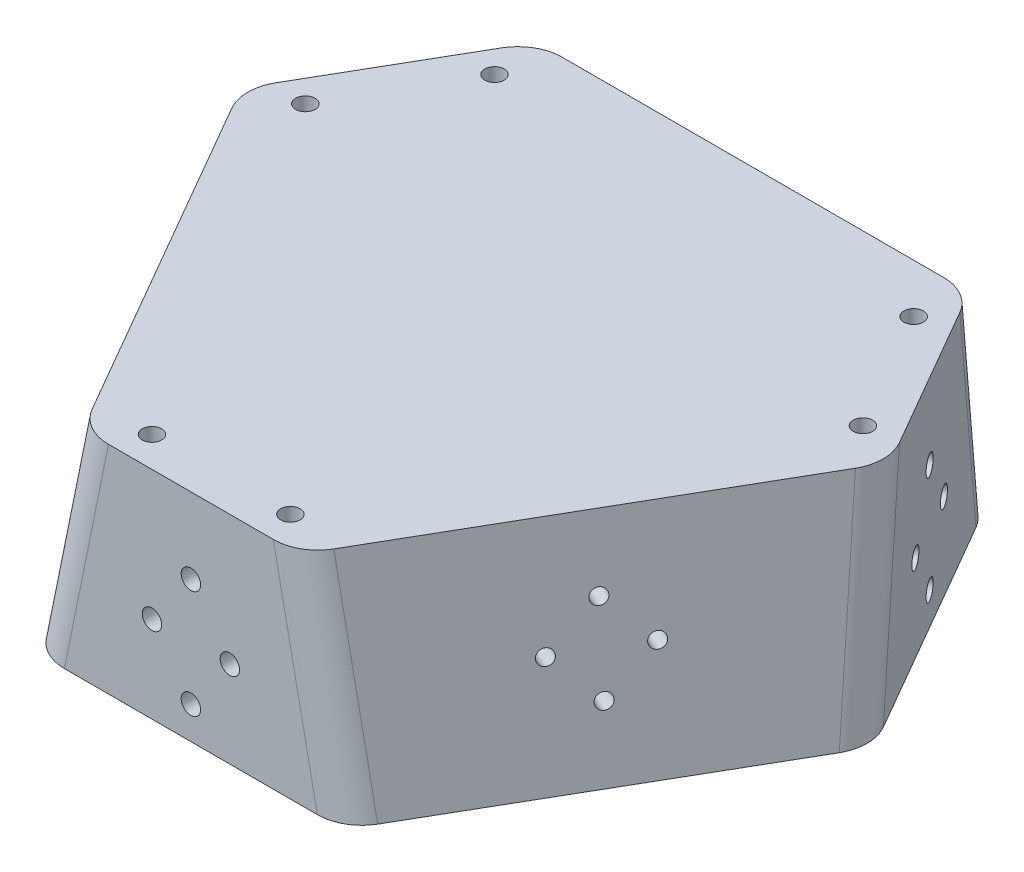
SolidWorks part; units mm, degrees
note: '?' marks a value the reader was unsure of.
ref_plane "Front Plane" through (0, 0, 0) normal (0, 0, 1) x (1, 0, 0)
ref_plane "Top Plane" through (0, 0, 0) normal (0, 1, 0) x (1, 0, 0)
ref_plane "Right Plane" through (0, 0, 0) normal (1, 0, 0) x (0, 0, -1)
sketch "Sketch1" plane through (0, 0, 0) normal (0, 1, 0) x (1, 0, 0)
  line L0 (-50, 57.735) -> (50, 57.735)
  line L1 (75, 14.4338) -> (25, -72.1688)
  line L2 (-25, -72.1688) -> (-75, 14.4338)
  line L3 (0, 0) -> (-50, -28.8675) construction
  line L4 (0, 0) -> (0, 57.735) construction
  line L5 (0, 0) -> (50, -28.8675) construction
  line L6 (-50, 57.735) -> (-75, 14.4338)
  line L7 (-25, -72.1688) -> (25, -72.1688)
  line L8 (50, 57.735) -> (75, 14.4338)
  line L9 (-100, 57.735) -> (-50, 57.735) construction
  line L10 (-75, 14.4338) -> (-100, 57.735) construction
  line L11 (50, 57.735) -> (100, 57.735) construction
  line L12 (100, 57.735) -> (75, 14.4338) construction
  line L13 (25, -72.1688) -> (0, -115.4701) construction
  line L14 (0, -115.4701) -> (-25, -72.1688) construction
  dimension "D1" = 50
  dimension "D2" = 100
extrude "Boss-Extrude1" add sketch "Sketch1" along normal blind 50
ref_plane "Plane2" through (0, 0, 0) normal (0.5, 0, -0.866) x (-0.866, 0, -0.5)
ref_plane "Plane3" through (0, 0, 0) normal (-0.5, 0, -0.866) x (-0.866, 0, 0.5)
sketch "Sketch2" plane through (0, 0, 0) normal (1, 0, 0) x (0, 0, -1)
  line L0 (57.735, 50) -> (66.5514, 0)
  line L1 (66.5514, 0) -> (57.735, 0)
  line L4 (14.4338, 0) -> (57.735, 0)
  line L5 (57.735, 0) -> (57.735, 50)
  line L6 (57.735, 50) -> (14.4338, 50)
  line L7 (14.4338, 50) -> (14.4338, 0)
  line L8 (14.4338, 0) -> (57.735, 0) construction
  line L9 (57.735, 0) -> (57.735, 50)
  line L10 (57.735, 50) -> (14.4338, 50) construction
  line L11 (14.4338, 50) -> (14.4338, 0) construction
  dimension "ThrusterAngle" = 10
extrude "Boss-Extrude2" add sketch "Sketch2" along normal up to surface and the other way up to surface up to face at (62.5, 25, -36.0844) other way up to face at (-62.5, 25, -36.0844)
sketch "Sketch7" plane through (0, 0, 0) normal (-0.5, 0, -0.866) x (-0.866, 0, 0.5)
  line L0 (57.735, 50) -> (57.735, 0) construction
  line L1 (57.735, 50) -> (57.735, 0)
  line L2 (57.735, 50) -> (66.5514, 0)
  line L3 (66.5514, 0) -> (57.735, 0)
  dimension "D1" = 10
extrude "Boss-Extrude3" add sketch "Sketch7" along normal up to surface and the other way up to surface up to face at (-61.2275, 25, -38.2885) other way up to face at (0, 25, 72.1688)
sketch "Sketch8" plane through (0, 0, 0) normal (0.5, 0, -0.866) x (-0.866, 0, -0.5)
  line L0 (-57.735, 50) -> (-57.735, 0) construction
  line L1 (-57.735, 50) -> (-57.735, 0)
  line L2 (-57.735, 50) -> (-66.5514, 0)
  line L3 (-66.5514, 0) -> (-57.735, 0)
  dimension "D1" = 10
extrude "Boss-Extrude4" add sketch "Sketch8" along normal up to surface and the other way up to surface up to face at (61.2275, 25, -38.2885) other way up to face at (-2.5451, 25, 72.1688)
sketch "Sketch9" plane through (0, 0, 0) normal (0, -1, 0) x (1, 0, 0)
  line L0 (-57.6795, -14.4338) -> (-41.3397, -42.735)
  line L1 (-41.3397, -42.735) -> (41.3397, -42.735)
  line L2 (41.3397, -42.735) -> (57.6795, -14.4338)
  line L3 (57.6795, -14.4338) -> (16.3397, 57.1688)
  line L4 (16.3397, 57.1688) -> (-16.3397, 57.1688)
  line L5 (-16.3397, 57.1688) -> (-57.6795, -14.4338)
  line L6 (-75, -14.4338) -> (-50, -57.735)
  line L7 (-25, 72.1688) -> (-75, -14.4338)
  line L8 (25, 72.1688) -> (-25, 72.1688)
  line L9 (75, -14.4338) -> (25, 72.1688)
  line L10 (50, -57.735) -> (75, -14.4338)
  line L11 (-50, -57.735) -> (50, -57.735)
  line L12 (-75, -14.4338) -> (-50, -57.735) construction
  line L13 (-25, 72.1688) -> (-75, -14.4338) construction
  line L14 (25, 72.1688) -> (-25, 72.1688) construction
  line L15 (75, -14.4338) -> (25, 72.1688) construction
  line L16 (50, -57.735) -> (75, -14.4338) construction
  line L17 (-50, -57.735) -> (50, -57.735) construction
  dimension "D1" = 0
  dimension "D2" = 15
extrude "Cut-Extrude1" cut sketch "Sketch9" against normal offset from surface (40 mm away) 10 up to face at (0, 50, 0)
ref_axis "Axis1" through (0, -2.5, 0) along (0, 1, 0)?
sketch "Sketch3" plane through (0, 11.381, -64.5446) normal (0, 0.1736, -0.9848) x (-1, 0, 0)
  line L0 (0, 39.2148) -> (0, 13.8291) construction
  line L1 (-50, 39.2148) -> (50, 39.2148) construction
  line L2 (0, 13.8291) -> (0, -11.5565) construction
  line L3 (-44.9099, -11.5565) -> (44.9099, -11.5565) construction
  line L4 (0, 23.3291) -> (9.5, 13.8291) construction
  line L5 (0, 23.3291) -> (-9.5, 13.8291) construction
  line L6 (9.5, 13.8291) -> (0, 4.3291) construction
  line L7 (-9.5, 13.8291) -> (0, 4.3291) construction
  line L8 (0, 23.3291) -> (0, 4.3291) construction
  line L9 (9.5, 13.8291) -> (-9.5, 13.8291) construction
  dimension "D1" = 19
  dimension "D2" = 19
hole_wizard "M3 Clearance Hole1" positions "3DSketch1" profile "Sketch10" hole size "M3" standard "ANSI Metric"
sketch3d "3DSketch1"
  point P0 (0, 34.3557, -60.4935)
  point P3 (9.5, 25, -62.1432)
  point P6 (0, 15.6443, -63.7929)
  point P9 (-9.5, 25, -62.1432)
sketch "Sketch10" plane through (0, 34.3557, -60.4935) normal (1, 0, 0) x (0, 0.9848, 0.1736)
  line L0 (0, 0) -> (0, 50)
  line L1 (0, 50) -> (1.7, 48.9785)
  line L2 (1.7, 48.9785) -> (1.7, 0)
  line L5 (1.7, 0) -> (0, 0)
  line L10 (0, 50) -> (-1.7, 48.9785) construction
  line L11 (0, -6.35) -> (0, 107.95) construction
  dimension "Hole Dia." = 3.4
  dimension "Hole Depth" = 50
  dimension "Drill Angle" = 118
pattern_circular "CirPattern6" count 3 every 120 about axis through (0, -2.5, 0) along (0, 1, 0) of "M3 Clearance Hole1"
sketch "Sketch12" plane through (-49.5096, 0, -28.5844) normal (0.866, 0, 0.5) x (0.5, 0, -0.866)
  line L0 (-16.3397, 20) -> (16.3397, 20) construction
  line L1 (-16.3397, 40) -> (-16.3397, 0) construction
  line L2 (16.3397, 40) -> (16.3397, 0) construction
  line L3 (0, 40) -> (0, 0) construction
  line L4 (16.3397, 40) -> (-16.3397, 40) construction
  line L5 (-16.3397, 0) -> (16.3397, 0) construction
  line L6 (-9, 20) -> (0, 32.5) construction
  line L7 (-4.525, 17.4164) -> (-4.525, 22.5836)
  line L8 (-4.525, 22.5836) -> (-9, 25.1673)
  line L9 (-9, 25.1673) -> (-13.475, 22.5836)
  line L10 (-13.475, 22.5836) -> (-13.475, 17.4164)
  line L11 (-13.475, 17.4164) -> (-9, 14.8327)
  line L12 (-9, 14.8327) -> (-4.525, 17.4164)
  line L13 (9, 14.8327) -> (13.475, 17.4164)
  line L14 (13.475, 17.4164) -> (13.475, 22.5836)
  line L15 (13.475, 22.5836) -> (9, 25.1673)
  line L16 (9, 25.1673) -> (4.525, 22.5836)
  line L17 (4.525, 22.5836) -> (4.525, 17.4164)
  line L18 (4.525, 17.4164) -> (9, 14.8327)
  line L19 (4.475, 4.9164) -> (4.475, 10.0836)
  line L20 (4.475, 10.0836) -> (0, 12.6673)
  line L21 (0, 12.6673) -> (-4.475, 10.0836)
  line L22 (-4.475, 10.0836) -> (-4.475, 4.9164)
  line L23 (-4.475, 4.9164) -> (0, 2.3327)
  line L24 (0, 2.3327) -> (4.475, 4.9164)
  line L25 (4.475, 29.9164) -> (4.475, 35.0836)
  line L26 (4.475, 35.0836) -> (0, 37.6673)
  line L27 (0, 37.6673) -> (-4.475, 35.0836)
  line L28 (-4.475, 35.0836) -> (-4.475, 29.9164)
  line L29 (-4.475, 29.9164) -> (0, 27.3327)
  line L30 (0, 27.3327) -> (4.475, 29.9164)
  line L31 (0, 32.5) -> (9, 20) construction
  line L32 (9, 20) -> (0, 7.5) construction
  line L33 (0, 7.5) -> (-9, 20) construction
  circle A0 centre (-9, 20) radius 4.475 construction
  circle A1 centre (9, 20) radius 4.475 construction
  circle A2 centre (0, 7.5) radius 4.475 construction
  circle A3 centre (0, 32.5) radius 4.475 construction
  point P48 (0, 32.5)
  point P51 (-9, 20)
  point P54 (9, 20)
  point P57 (0, 7.5)
  dimension "D1" = 8.95
  dimension "D2" = 25
  dimension "D3" = 18
extrude "Cut-Extrude2" cut sketch "Sketch12" against normal blind 3.5
sketch "Sketch13" plane through (-52.5407, 0, -30.3344) normal (0.866, 0, 0.5) x (0.5, 0, -0.866)
  point P0 (-9, 20)
  point P1 (9, 20)
  point P2 (0, 7.5)
  point P3 (0, 32.5)
hole_wizard "#8 Clearance Hole1" positions "Sketch13" profile "Sketch14" hole size "#8" standard "ANSI Inch"
sketch "Sketch14" plane through (-57.0407, 20, -22.5402) normal (0, 1, 0) x (0.5, 0, -0.866)
  line L0 (0, 0) -> (0, 50)
  line L1 (0, 50) -> (2.2479, 48.6493)
  line L2 (2.2479, 48.6493) -> (2.2479, 0)
  line L5 (2.2479, 0) -> (0, 0)
  line L10 (0, 50) -> (-2.2479, 48.6493) construction
  line L11 (0, -6.35) -> (0, 107.95) construction
  dimension "Hole Dia." = 4.4958
  dimension "Hole Depth" = 50
  dimension "Drill Angle" = 118
sketch "Sketch15" plane through (0, 50, 0) normal (0, 1, 0) x (1, 0, 0)
  line L0 (-64.4378, 18.728) -> (-48.4378, 46.4408) construction
  line L1 (-50, 57.735) -> (-75, 14.4338) construction
  line L2 (-64.4378, 18.728) -> (-75, 14.4338) construction
  line L3 (-48.4378, 46.4408) -> (-50, 57.735) construction
  point P9 (-64.4378, 18.728)
  point P10 (-48.4378, 46.4408)
  dimension "D1" = 7
  dimension "D2" = 32
sketch "Sketch18" plane through (0, 0, 0) normal (0, -1, 0) x (1, 0, 0)
  point P0 (-64.4378, -18.728)
  point P1 (-48.4378, -46.4408)
hole_wizard "CBORE for #8 Socket Head Cap Screw1" positions "Sketch18" profile "Sketch19" counterbore size "#8" standard "ANSI Inch"
sketch "Sketch19" plane through (-64.4378, 0, -18.728) normal (1, 0, 0) x (0, 0, -1)
  line L0 (0, 0) -> (0, 60)
  line L1 (0, 60) -> (2.2479, 58.6493)
  line L2 (2.2479, 58.6493) -> (2.2479, 12.7)
  line L3 (2.2479, 12.7) -> (3.9687, 12.7)
  line L4 (3.9687, 12.7) -> (3.9688, 0)
  line L5 (3.9688, 0) -> (0, 0)
  line L10 (0, 60) -> (-2.2479, 58.6493) construction
  line L11 (0, -6.35) -> (0, 107.95) construction
  dimension "Hole Dia." = 4.4958
  dimension "Hole Depth" = 60
  dimension "C'Bore Dia." = 7.9375
  dimension "C'Bore Depth" = 12.7
  dimension "Drill Angle" = 118
pattern_circular "CirPattern7" count 3 every 120 about axis through (0, 0, 0) along (0, 1, 0) of "#8 Clearance Hole1", "Cut-Extrude2", "CBORE for #8 Socket Head Cap Screw1"
sketch "Be Happy" plane through (0, 50, 0) normal (0, 1, 0) x (1, 0, 0)
  line L0 (-50, 57.735) -> (-40, 57.735)
  line L1 (50, 57.735) -> (-50, 57.735) construction
  point P4 (0, 0)
  dimension "ThrusterAngle" = 10
fillet "Fillet1" radius 10 6 edges at (47.4549, 25, -62.1432) (-47.4549, 25, -62.1432) (-77.5451, 25, -10.0256) (-30.0901, 25, 72.1688) (77.5451, 25, -10.0256) (30.0901, 25, 72.1688)
equation "\"ThrusterAngle\"=10"
equation "\"ThrusterAngle@Be Happy\"= 10"
equation "\"ThrusterAngle@Sketch2\"= \"ThrusterAngle\""
equation "\"D1@Sketch7\"= \"ThrusterAngle\""
equation "\"D1@Sketch8\"=\"ThrusterAngle\""
